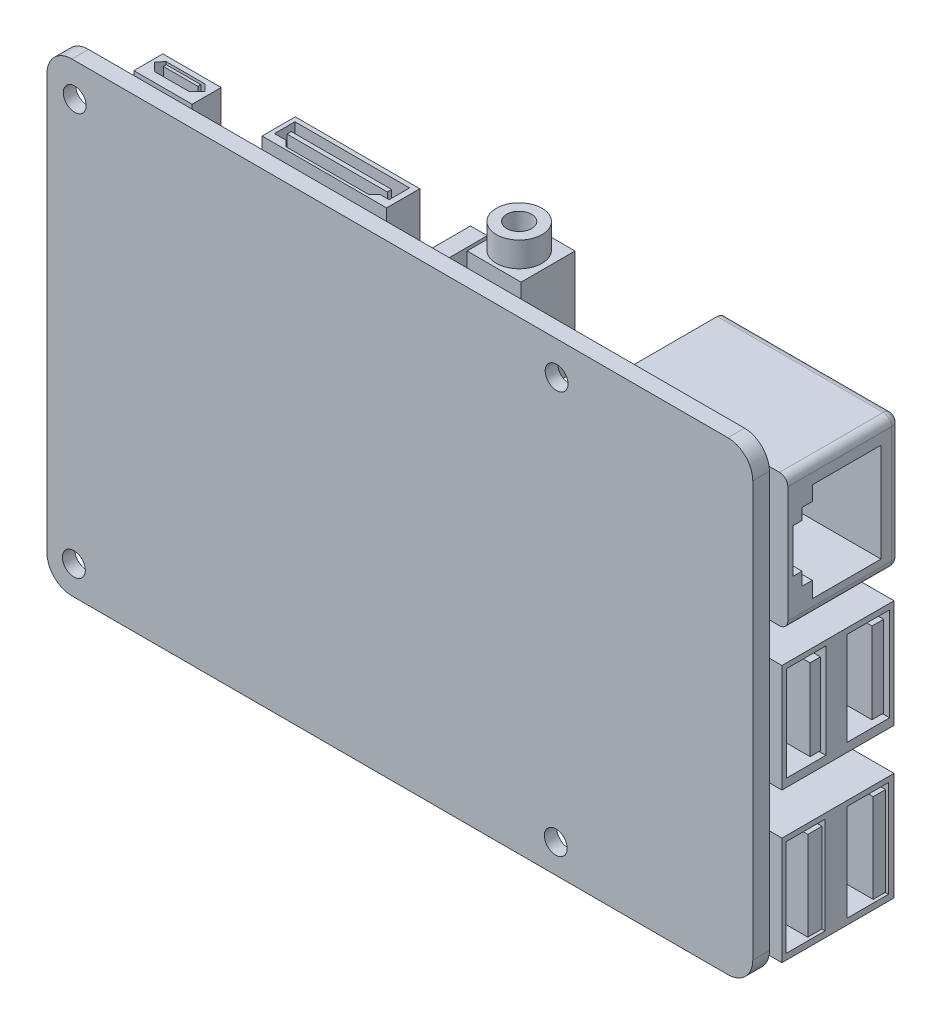
SolidWorks part; units mm, degrees
ref_plane "Front Plane" through (0, 0, 0) normal (0, 0, 1) x (1, 0, 0)
ref_plane "Top Plane" through (0, 0, 0) normal (0, 1, 0) x (1, 0, 0)
ref_plane "Right Plane" through (0, 0, 0) normal (1, 0, 0) x (0, 0, -1)
sketch "Sketch1" plane through (0, 0, 0) normal (0, 0, 1) x (1, 0, 0)
  line L1 (-42.5, 28) -> (42.5, 28)
  line L2 (-42.5, 28) -> (-42.5, -28)
  line L3 (-42.5, -28) -> (42.5, -28)
  line L4 (42.5, 28) -> (42.5, -28)
  line L5 (-42.5, 28) -> (42.5, -28) construction
  line L6 (-42.5, -28) -> (42.5, 28) construction
  point P0 (0, 0)
  dimension "D1" = 85
  dimension "D2" = 56
extrude "Boss-Extrude1" add sketch "Sketch1" along normal blind 2
fillet "Fillet1" radius 3 4 edges at (42.5, -28, 1) (42.5, 28, 1) (-42.5, 28, 1) (-42.5, -28, 1)
sketch "Sketch2" plane through (0, 0, 0) normal (0, 0, -1) x (-1, 0, 0)
  circle A0 centre (39.161, -24.5985) radius 3.1
  circle A1 centre (-18.839, -24.5986) radius 3.1
  circle A2 centre (39.161, 23.9785) radius 3.1
  circle A3 centre (-18.839, 23.9761) radius 3.1
  dimension "D1" = 6.2
  dimension "D3" = 6.2
  dimension "D2" = 58
  dimension "D4" = 58
extrude "Cut-Extrude2" cut sketch "Sketch2" against normal blind 0.5
sketch "Sketch3" plane through (0, 0, 0.5) normal (0, 0, -1) x (-1, 0, 0)
  line L0 (42.5, 25) -> (42.5, -25) construction
  line L1 (-42.5, -25) -> (-42.5, 25) construction
  line L2 (-39.5, 28) -> (39.5, 28) construction
  line L3 (39.5, -28) -> (-39.5, -28) construction
  circle A0 centre (39.161, 23.9785) radius 1.375
  circle A1 centre (-18.8764, 23.9785) radius 1.375
  circle A2 centre (-18.7753, -24.5312) radius 1.375
  circle A3 centre (39.2622, -24.5312) radius 1.375
  dimension "D1" = 2.75
  dimension "D2" = 2.75
  dimension "D9" = 2.75
  dimension "D10" = 2.75
  dimension "D3" = 58.0375
  dimension "D4" = 48.5097
  dimension "D5" = 3.339
  dimension "D6" = 23.6236
  dimension "D7" = 4.0215
  dimension "D8" = 3.4688
extrude "Cut-Extrude3" cut sketch "Sketch3" against normal blind 10.5
sketch "Sketch4" plane through (0, 0, 0) normal (0, 0, -1) x (-1, 0, 0)
  line L0 (-39.5, 28) -> (39.5, 28) construction
  line L1 (-23.7207, 9.5) -> (-44.7207, 9.5)
  line L2 (-23.7207, 9.5) -> (-23.7207, 25.5)
  line L3 (-23.7207, 25.5) -> (-44.7207, 25.5)
  line L4 (-44.7207, 9.5) -> (-44.7207, 25.5)
  line L5 (-23.7207, 9.5) -> (-44.7207, 25.5) construction
  line L6 (-23.7207, 25.5) -> (-44.7207, 9.5) construction
  point P0 (-34.2207, 17.5)
  dimension "D1" = 2.5
  dimension "D2" = 21
  dimension "D3" = 16
  dimension "D4" = 10.5
extrude "Boss-Extrude2" add sketch "Sketch4" along normal blind 13.5
fillet "Fillet2" radius 1 5 edges at (34.2207, 25.5, -13.5) (34.2207, 9.5, -13.5) (44.7207, 9.5, -6.75) (44.7207, 25.5, -6.75) (44.7207, 17.5, -13.5)
sketch "Sketch5" plane through (44.7207, 0, 0) normal (1, 0, 0) x (0, 0, -1)
  line L0 (0.6237, 20.117) -> (0.6237, 14.8349)
  line L1 (0.6237, 14.8349) -> (1.7111, 14.8349)
  line L2 (1.7111, 14.8349) -> (1.7111, 13.2605)
  line L3 (1.7111, 13.2605) -> (2.9538, 13.2605)
  line L4 (2.9538, 13.2605) -> (2.9538, 11.3427)
  line L5 (2.9538, 11.3427) -> (11.2173, 11.3427)
  line L6 (11.2173, 11.3427) -> (11.2173, 23.2197)
  line L7 (11.2173, 23.2197) -> (2.9538, 23.2197)
  line L8 (2.9538, 23.2197) -> (2.9538, 21.4786)
  line L9 (2.9538, 21.4786) -> (1.7111, 21.4786)
  line L10 (1.7111, 21.4786) -> (1.7111, 20.117)
  line L11 (1.7111, 20.117) -> (0.6237, 20.117)
extrude "Cut-Extrude4" cut sketch "Sketch5" against normal blind 18.5
sketch "Sketch7" plane through (0, 0, 0) normal (0, 0, -1) x (-1, 0, 0)
  line L0 (-39.5, 28) -> (39.5, 28) construction
  line L1 (-44.0111, 5.5) -> (-27.0111, 5.5)
  line L2 (-44.0111, 5.5) -> (-44.0111, -7.5)
  line L3 (-44.0111, -7.5) -> (-27.0111, -7.5)
  line L4 (-27.0111, 5.5) -> (-27.0111, -7.5)
  line L5 (-44.0111, 5.5) -> (-27.0111, -7.5) construction
  line L6 (-44.0111, -7.5) -> (-27.0111, 5.5) construction
  point P0 (-35.5111, -1)
  dimension "D1" = 29
  dimension "D2" = 13
  dimension "D3" = 17
extrude "Boss-Extrude3" add sketch "Sketch7" along normal blind 13.5
sketch "Sketch8" plane through (44.0111, 0, 0) normal (1, 0, 0) x (0, 0, -1)
  line L1 (7.8471, 4.8156) -> (12.9735, 4.8156)
  line L2 (7.8471, 4.8156) -> (7.8471, -6.4468)
  line L3 (7.8471, -6.4468) -> (12.9735, -6.4468)
  line L4 (12.9735, 4.8156) -> (12.9735, -6.4468)
  line L5 (7.8471, 4.8156) -> (12.9735, -6.4468) construction
  line L6 (7.8471, -6.4468) -> (12.9735, 4.8156) construction
  line L7 (0.546, 4.8933) -> (5.284, 4.8933)
  line L8 (0.546, 4.8933) -> (0.546, -6.5244)
  line L9 (0.546, -6.5244) -> (5.284, -6.5244)
  line L10 (5.284, 4.8933) -> (5.284, -6.5244)
  line L11 (0.546, 4.8933) -> (5.284, -6.5244) construction
  line L12 (0.546, -6.5244) -> (5.284, 4.8933) construction
  point P0 (10.4103, -0.8156)
  point P5 (2.915, -0.8156)
extrude "Cut-Extrude5" cut sketch "Sketch8" against normal blind 13.5
sketch "Sketch9" plane through (30.5111, 0, 0) normal (1, 0, 0) x (0, 0, -1)
  line L1 (10.8479, 4.1943) -> (12.246, 4.1943)
  line L2 (10.8479, 4.1943) -> (10.8479, -5.5924)
  line L3 (10.8479, -5.5924) -> (12.246, -5.5924)
  line L4 (12.246, 4.1943) -> (12.246, -5.5924)
  line L5 (10.8479, 4.1943) -> (12.246, -5.5924) construction
  line L6 (10.8479, -5.5924) -> (12.246, 4.1943) construction
  line L7 (3.3914, 4.0778) -> (4.6341, 4.0778)
  line L8 (3.3914, 4.0778) -> (3.3914, -5.7089)
  line L9 (3.3914, -5.7089) -> (4.6341, -5.7089)
  line L10 (4.6341, 4.0778) -> (4.6341, -5.7089)
  line L11 (3.3914, 4.0778) -> (4.6341, -5.7089) construction
  line L12 (3.3914, -5.7089) -> (4.6341, 4.0778) construction
  point P0 (11.5469, -0.699)
  point P5 (4.0128, -0.8156)
  dimension "D1" = 0.6214
extrude "Boss-Extrude4" add sketch "Sketch9" along normal blind 13.5
sketch "Sketch10" plane through (0, 0, 0) normal (0, 0, -1) x (-1, 0, 0)
  line L0 (-39.5, 28) -> (39.5, 28) construction
  line L1 (-44.0178, -12.5) -> (-27.0044, -12.5)
  line L2 (-44.0178, -12.5) -> (-44.0178, -25.5)
  line L3 (-44.0178, -25.5) -> (-27.0044, -25.5)
  line L4 (-27.0044, -12.5) -> (-27.0044, -25.5)
  line L5 (-44.0178, -12.5) -> (-27.0044, -25.5) construction
  line L6 (-44.0178, -25.5) -> (-27.0044, -12.5) construction
  point P0 (-35.5111, -19)
  dimension "D1" = 47
  dimension "D2" = 13
  dimension "D3" = 17.0134
extrude "Boss-Extrude5" add sketch "Sketch10" along normal blind 13.5
sketch "Sketch11" plane through (44.0178, 0, 0) normal (1, 0, 0) x (0, 0, -1)
  line L1 (7.8471, -13.1265) -> (12.8181, -13.1265)
  line L2 (7.8471, -13.1265) -> (7.8471, -24.7773)
  line L3 (7.8471, -24.7773) -> (12.8181, -24.7773)
  line L4 (12.8181, -13.1265) -> (12.8181, -24.7773)
  line L5 (7.8471, -13.1265) -> (12.8181, -24.7773) construction
  line L6 (7.8471, -24.7773) -> (12.8181, -13.1265) construction
  line L7 (0.4891, -13.1265) -> (5.2063, -13.1265)
  line L8 (0.4891, -13.1265) -> (0.4891, -24.7773)
  line L9 (0.4891, -24.7773) -> (5.2063, -24.7773)
  line L10 (5.2063, -13.1265) -> (5.2063, -24.7773)
  line L11 (0.4891, -13.1265) -> (5.2063, -24.7773) construction
  line L12 (0.4891, -24.7773) -> (5.2063, -13.1265) construction
  point P0 (10.3326, -18.9519)
  point P5 (2.8477, -18.9519)
extrude "Cut-Extrude6" cut sketch "Sketch11" against normal blind 13.5
sketch "Sketch12" plane through (30.5178, 0, 0) normal (1, 0, 0) x (0, 0, -1)
  line L1 (12.479, -13.6702) -> (10.9825, -13.6702)
  line L2 (12.479, -13.6702) -> (12.479, -24.3889)
  line L3 (12.479, -24.3889) -> (10.9825, -24.3889)
  line L4 (10.9825, -13.6702) -> (10.9825, -24.3889)
  line L5 (12.479, -13.6702) -> (10.9825, -24.3889) construction
  line L6 (12.479, -24.3889) -> (10.9825, -13.6702) construction
  line L7 (3.1092, -13.6702) -> (4.8168, -13.6702)
  line L8 (3.1092, -13.6702) -> (3.1092, -24.3889)
  line L9 (3.1092, -24.3889) -> (4.8168, -24.3889)
  line L10 (4.8168, -13.6702) -> (4.8168, -24.3889)
  line L11 (3.1092, -13.6702) -> (4.8168, -24.3889) construction
  line L12 (3.1092, -24.3889) -> (4.8168, -13.6702) construction
  point P0 (11.7307, -19.0296)
  point P6 (3.963, -19.0296)
extrude "Boss-Extrude6" add sketch "Sketch12" along normal blind 13.5
sketch "Sketch13" plane through (0, 0, 0) normal (0, 0, -1) x (-1, 0, 0)
  line L0 (42.5, 25) -> (42.5, -25) construction
  line L1 (-14.0854, -22.7565) -> (35.0854, -22.7565)
  line L2 (-14.0854, -22.7565) -> (-14.0854, -27.2565)
  line L3 (-14.0854, -27.2565) -> (35.0854, -27.2565)
  line L4 (35.0854, -22.7565) -> (35.0854, -27.2565)
  line L5 (-14.0854, -22.7565) -> (35.0854, -27.2565) construction
  line L6 (-14.0854, -27.2565) -> (35.0854, -22.7565) construction
  point P0 (10.5, -25.0065)
  dimension "D1" = 32
  dimension "D2" = 4.5
extrude "Boss-Extrude7" add sketch "Sketch13" along normal blind 2.5
sketch "Sketch14" plane through (0, 0, -2.5) normal (0, 0, -1) x (-1, 0, 0)
  line L0 (-11.0708, -26.0079) -> (-10.1069, -26.0079)
  line L1 (-13.5708, -26.0079) -> (-12.6069, -26.0079)
  line L2 (-13.5708, -26.0079) -> (-13.5708, -27.0079)
  line L3 (-13.5708, -27.0079) -> (-12.6069, -27.0079)
  line L4 (-12.6069, -26.0079) -> (-12.6069, -27.0079)
  line L5 (-13.5708, -26.0079) -> (-12.6069, -27.0079) construction
  line L6 (-13.5708, -27.0079) -> (-12.6069, -26.0079) construction
  line L7 (-10.1069, -26.0079) -> (-10.1069, -27.0079)
  line L8 (-11.0708, -27.0079) -> (-10.1069, -27.0079)
  line L9 (-11.0708, -26.0079) -> (-11.0708, -27.0079)
  line L10 (-8.5708, -26.0079) -> (-7.6069, -26.0079)
  line L11 (-7.6069, -26.0079) -> (-7.6069, -27.0079)
  line L12 (-8.5708, -27.0079) -> (-7.6069, -27.0079)
  line L13 (-8.5708, -26.0079) -> (-8.5708, -27.0079)
  line L14 (-6.0708, -26.0079) -> (-5.1069, -26.0079)
  line L15 (-5.1069, -26.0079) -> (-5.1069, -27.0079)
  line L16 (-6.0708, -27.0079) -> (-5.1069, -27.0079)
  line L17 (-6.0708, -26.0079) -> (-6.0708, -27.0079)
  line L18 (-3.5708, -26.0079) -> (-2.6069, -26.0079)
  line L19 (-2.6069, -26.0079) -> (-2.6069, -27.0079)
  line L20 (-3.5708, -27.0079) -> (-2.6069, -27.0079)
  line L21 (-3.5708, -26.0079) -> (-3.5708, -27.0079)
  line L22 (-1.0708, -26.0079) -> (-0.1069, -26.0079)
  line L23 (-0.1069, -26.0079) -> (-0.1069, -27.0079)
  line L24 (-1.0708, -27.0079) -> (-0.1069, -27.0079)
  line L25 (-1.0708, -26.0079) -> (-1.0708, -27.0079)
  line L26 (1.4292, -26.0079) -> (2.3931, -26.0079)
  line L27 (2.3931, -26.0079) -> (2.3931, -27.0079)
  line L28 (1.4292, -27.0079) -> (2.3931, -27.0079)
  line L29 (1.4292, -26.0079) -> (1.4292, -27.0079)
  line L30 (3.9292, -26.0079) -> (4.8931, -26.0079)
  line L31 (4.8931, -26.0079) -> (4.8931, -27.0079)
  line L32 (3.9292, -27.0079) -> (4.8931, -27.0079)
  line L33 (3.9292, -26.0079) -> (3.9292, -27.0079)
  line L34 (6.4292, -26.0079) -> (7.3931, -26.0079)
  line L35 (7.3931, -26.0079) -> (7.3931, -27.0079)
  line L36 (6.4292, -27.0079) -> (7.3931, -27.0079)
  line L37 (6.4292, -26.0079) -> (6.4292, -27.0079)
  line L38 (8.9292, -26.0079) -> (9.8931, -26.0079)
  line L39 (9.8931, -26.0079) -> (9.8931, -27.0079)
  line L40 (8.9292, -27.0079) -> (9.8931, -27.0079)
  line L41 (8.9292, -26.0079) -> (8.9292, -27.0079)
  line L42 (11.4292, -26.0079) -> (12.3931, -26.0079)
  line L43 (12.3931, -26.0079) -> (12.3931, -27.0079)
  line L44 (11.4292, -27.0079) -> (12.3931, -27.0079)
  line L45 (11.4292, -26.0079) -> (11.4292, -27.0079)
  line L46 (13.9292, -26.0079) -> (14.8931, -26.0079)
  line L47 (14.8931, -26.0079) -> (14.8931, -27.0079)
  line L48 (13.9292, -27.0079) -> (14.8931, -27.0079)
  line L49 (13.9292, -26.0079) -> (13.9292, -27.0079)
  line L50 (16.4292, -26.0079) -> (17.3931, -26.0079)
  line L51 (17.3931, -26.0079) -> (17.3931, -27.0079)
  line L52 (16.4292, -27.0079) -> (17.3931, -27.0079)
  line L53 (16.4292, -26.0079) -> (16.4292, -27.0079)
  line L54 (18.9292, -26.0079) -> (19.8931, -26.0079)
  line L55 (19.8931, -26.0079) -> (19.8931, -27.0079)
  line L56 (18.9292, -27.0079) -> (19.8931, -27.0079)
  line L57 (18.9292, -26.0079) -> (18.9292, -27.0079)
  line L58 (21.4292, -26.0079) -> (22.3931, -26.0079)
  line L59 (22.3931, -26.0079) -> (22.3931, -27.0079)
  line L60 (21.4292, -27.0079) -> (22.3931, -27.0079)
  line L61 (21.4292, -26.0079) -> (21.4292, -27.0079)
  line L62 (23.9292, -26.0079) -> (24.8931, -26.0079)
  line L63 (24.8931, -26.0079) -> (24.8931, -27.0079)
  line L64 (23.9292, -27.0079) -> (24.8931, -27.0079)
  line L65 (23.9292, -26.0079) -> (23.9292, -27.0079)
  line L66 (26.4292, -26.0079) -> (27.3931, -26.0079)
  line L67 (27.3931, -26.0079) -> (27.3931, -27.0079)
  line L68 (26.4292, -27.0079) -> (27.3931, -27.0079)
  line L69 (26.4292, -26.0079) -> (26.4292, -27.0079)
  line L70 (28.9292, -26.0079) -> (29.8931, -26.0079)
  line L71 (29.8931, -26.0079) -> (29.8931, -27.0079)
  line L72 (28.9292, -27.0079) -> (29.8931, -27.0079)
  line L73 (28.9292, -26.0079) -> (28.9292, -27.0079)
  line L74 (31.4292, -26.0079) -> (32.3931, -26.0079)
  line L75 (32.3931, -26.0079) -> (32.3931, -27.0079)
  line L76 (31.4292, -27.0079) -> (32.3931, -27.0079)
  line L77 (31.4292, -26.0079) -> (31.4292, -27.0079)
  line L78 (33.9292, -26.0079) -> (34.8931, -26.0079)
  line L79 (34.8931, -26.0079) -> (34.8931, -27.0079)
  line L80 (33.9292, -27.0079) -> (34.8931, -27.0079)
  line L81 (33.9292, -26.0079) -> (33.9292, -27.0079)
  line L82 (1.4292, -23.0147) -> (1.4292, -24.0147)
  line L83 (26.4292, -23.0147) -> (27.3931, -23.0147)
  line L84 (31.4292, -23.0147) -> (32.3931, -23.0147)
  line L85 (-7.6069, -23.0147) -> (-7.6069, -24.0147)
  line L86 (-3.5708, -24.0147) -> (-2.6069, -24.0147)
  line L87 (-1.0708, -23.0147) -> (-1.0708, -24.0147)
  line L88 (8.9292, -23.0147) -> (9.8931, -23.0147)
  line L89 (13.9292, -23.0147) -> (14.8931, -23.0147)
  line L90 (13.9292, -24.0147) -> (14.8931, -24.0147)
  line L91 (16.4292, -23.0147) -> (17.3931, -23.0147)
  line L92 (11.4292, -23.0147) -> (11.4292, -24.0147)
  line L93 (21.4292, -24.0147) -> (22.3931, -24.0147)
  line L94 (34.8931, -23.0147) -> (34.8931, -24.0147)
  line L95 (-11.0708, -24.0147) -> (-10.1069, -24.0147)
  line L96 (-0.1069, -23.0147) -> (-0.1069, -24.0147)
  line L97 (6.4292, -24.0147) -> (7.3931, -24.0147)
  line L98 (21.4292, -23.0147) -> (21.4292, -24.0147)
  line L99 (27.3931, -23.0147) -> (27.3931, -24.0147)
  line L100 (3.9292, -23.0147) -> (4.8931, -23.0147)
  line L101 (16.4292, -23.0147) -> (16.4292, -24.0147)
  line L102 (32.3931, -23.0147) -> (32.3931, -24.0147)
  line L103 (-13.5708, -23.0147) -> (-12.6069, -23.0147)
  line L104 (3.9292, -24.0147) -> (4.8931, -24.0147)
  line L105 (3.9292, -23.0147) -> (3.9292, -24.0147)
  line L106 (11.4292, -23.0147) -> (12.3931, -23.0147)
  line L107 (11.4292, -24.0147) -> (12.3931, -24.0147)
  line L108 (18.9292, -23.0147) -> (18.9292, -24.0147)
  line L109 (26.4292, -23.0147) -> (26.4292, -24.0147)
  line L110 (-13.5708, -24.0147) -> (-12.6069, -24.0147)
  line L111 (-5.1069, -23.0147) -> (-5.1069, -24.0147)
  line L112 (21.4292, -23.0147) -> (22.3931, -23.0147)
  line L113 (26.4292, -24.0147) -> (27.3931, -24.0147)
  line L114 (-2.6069, -23.0147) -> (-2.6069, -24.0147)
  line L115 (1.4292, -24.0147) -> (2.3931, -24.0147)
  line L116 (6.4292, -23.0147) -> (7.3931, -23.0147)
  line L117 (8.9292, -23.0147) -> (8.9292, -24.0147)
  line L118 (23.9292, -23.0147) -> (23.9292, -24.0147)
  line L119 (28.9292, -23.0147) -> (29.8931, -23.0147)
  line L120 (-13.5708, -23.0147) -> (-12.6069, -24.0147) construction
  line L121 (-11.0708, -23.0147) -> (-11.0708, -24.0147)
  line L122 (-8.5708, -24.0147) -> (-7.6069, -24.0147)
  line L123 (-6.0708, -23.0147) -> (-6.0708, -24.0147)
  line L124 (-1.0708, -24.0147) -> (-0.1069, -24.0147)
  line L125 (6.4292, -23.0147) -> (6.4292, -24.0147)
  line L126 (8.9292, -24.0147) -> (9.8931, -24.0147)
  line L127 (24.8931, -23.0147) -> (24.8931, -24.0147)
  line L128 (33.9292, -24.0147) -> (34.8931, -24.0147)
  line L129 (18.9292, -23.0147) -> (19.8931, -23.0147)
  line L130 (31.4292, -23.0147) -> (31.4292, -24.0147)
  line L131 (-10.1069, -23.0147) -> (-10.1069, -24.0147)
  line L132 (-3.5708, -23.0147) -> (-3.5708, -24.0147)
  line L133 (7.3931, -23.0147) -> (7.3931, -24.0147)
  line L134 (12.3931, -23.0147) -> (12.3931, -24.0147)
  line L135 (13.9292, -23.0147) -> (13.9292, -24.0147)
  line L136 (23.9292, -23.0147) -> (24.8931, -23.0147)
  line L137 (-12.6069, -23.0147) -> (-12.6069, -24.0147)
  line L138 (16.4292, -24.0147) -> (17.3931, -24.0147)
  line L139 (29.8931, -23.0147) -> (29.8931, -24.0147)
  line L140 (-11.0708, -23.0147) -> (-10.1069, -23.0147)
  line L141 (-6.0708, -23.0147) -> (-5.1069, -23.0147)
  line L142 (9.8931, -23.0147) -> (9.8931, -24.0147)
  line L143 (17.3931, -23.0147) -> (17.3931, -24.0147)
  line L144 (28.9292, -24.0147) -> (29.8931, -24.0147)
  line L145 (33.9292, -23.0147) -> (33.9292, -24.0147)
  line L146 (-8.5708, -23.0147) -> (-7.6069, -23.0147)
  line L147 (-8.5708, -23.0147) -> (-8.5708, -24.0147)
  line L148 (23.9292, -24.0147) -> (24.8931, -24.0147)
  line L149 (31.4292, -24.0147) -> (32.3931, -24.0147)
  line L150 (-3.5708, -23.0147) -> (-2.6069, -23.0147)
  line L151 (2.3931, -23.0147) -> (2.3931, -24.0147)
  line L152 (18.9292, -24.0147) -> (19.8931, -24.0147)
  line L153 (33.9292, -23.0147) -> (34.8931, -23.0147)
  line L154 (-1.0708, -23.0147) -> (-0.1069, -23.0147)
  line L155 (4.8931, -23.0147) -> (4.8931, -24.0147)
  line L156 (19.8931, -23.0147) -> (19.8931, -24.0147)
  line L157 (22.3931, -23.0147) -> (22.3931, -24.0147)
  line L158 (-13.5708, -24.0147) -> (-12.6069, -23.0147) construction
  line L159 (-13.5708, -23.0147) -> (-13.5708, -24.0147)
  line L160 (-6.0708, -24.0147) -> (-5.1069, -24.0147)
  line L161 (1.4292, -23.0147) -> (2.3931, -23.0147)
  line L162 (14.8931, -23.0147) -> (14.8931, -24.0147)
  line L163 (28.9292, -23.0147) -> (28.9292, -24.0147)
  point P0 (-13.0889, -26.5079)
  point P6 (-13.0889, -23.5147)
  dimension "D1" = 0.9639
  dimension "D2" = 1
  dimension "D4" = 0.9639
  dimension "D5" = 1
  dimension "D3" = 20
extrude "Cut-Extrude7" cut sketch "Sketch14" against normal blind 2.5
sketch "Sketch15" plane through (0, 0, -2.5) normal (0, 0, -1) x (-1, 0, 0)
  line L0 (-12.6069, -27.0079) -> (-12.6069, -26.0079) construction
  line L1 (-13.5708, -26.0079) -> (-12.6069, -26.0079)
  line L2 (-13.5708, -26.0079) -> (-13.5708, -27.0079)
  line L3 (-13.5708, -27.0079) -> (-12.6069, -27.0079)
  line L4 (-12.6069, -26.0079) -> (-12.6069, -27.0079)
  line L5 (-13.5708, -26.0079) -> (-12.6069, -27.0079) construction
  line L6 (-13.5708, -27.0079) -> (-12.6069, -26.0079) construction
  line L7 (-13.5708, -27.0079) -> (-12.6069, -27.0079) construction
  line L8 (-12.6069, -26.0079) -> (-13.5708, -26.0079) construction
  line L9 (-13.5708, -26.0079) -> (-13.5708, -27.0079) construction
  line L10 (-11.0708, -26.0079) -> (-10.1069, -26.0079)
  line L11 (-10.1069, -26.0079) -> (-10.1069, -27.0079)
  line L12 (-11.0708, -27.0079) -> (-10.1069, -27.0079)
  line L13 (-11.0708, -26.0079) -> (-11.0708, -27.0079)
  line L14 (-8.5708, -26.0079) -> (-7.6069, -26.0079)
  line L15 (-7.6069, -26.0079) -> (-7.6069, -27.0079)
  line L16 (-8.5708, -27.0079) -> (-7.6069, -27.0079)
  line L17 (-8.5708, -26.0079) -> (-8.5708, -27.0079)
  line L18 (-6.0708, -26.0079) -> (-5.1069, -26.0079)
  line L19 (-5.1069, -26.0079) -> (-5.1069, -27.0079)
  line L20 (-6.0708, -27.0079) -> (-5.1069, -27.0079)
  line L21 (-6.0708, -26.0079) -> (-6.0708, -27.0079)
  line L22 (-3.5708, -26.0079) -> (-2.6069, -26.0079)
  line L23 (-2.6069, -26.0079) -> (-2.6069, -27.0079)
  line L24 (-3.5708, -27.0079) -> (-2.6069, -27.0079)
  line L25 (-3.5708, -26.0079) -> (-3.5708, -27.0079)
  line L26 (-1.0708, -26.0079) -> (-0.1069, -26.0079)
  line L27 (-0.1069, -26.0079) -> (-0.1069, -27.0079)
  line L28 (-1.0708, -27.0079) -> (-0.1069, -27.0079)
  line L29 (-1.0708, -26.0079) -> (-1.0708, -27.0079)
  line L30 (1.4292, -26.0079) -> (2.3931, -26.0079)
  line L31 (2.3931, -26.0079) -> (2.3931, -27.0079)
  line L32 (1.4292, -27.0079) -> (2.3931, -27.0079)
  line L33 (1.4292, -26.0079) -> (1.4292, -27.0079)
  line L34 (3.9292, -26.0079) -> (4.8931, -26.0079)
  line L35 (4.8931, -26.0079) -> (4.8931, -27.0079)
  line L36 (3.9292, -27.0079) -> (4.8931, -27.0079)
  line L37 (3.9292, -26.0079) -> (3.9292, -27.0079)
  line L38 (6.4292, -26.0079) -> (7.3931, -26.0079)
  line L39 (7.3931, -26.0079) -> (7.3931, -27.0079)
  line L40 (6.4292, -27.0079) -> (7.3931, -27.0079)
  line L41 (6.4292, -26.0079) -> (6.4292, -27.0079)
  line L42 (8.9292, -26.0079) -> (9.8931, -26.0079)
  line L43 (9.8931, -26.0079) -> (9.8931, -27.0079)
  line L44 (8.9292, -27.0079) -> (9.8931, -27.0079)
  line L45 (8.9292, -26.0079) -> (8.9292, -27.0079)
  line L46 (11.4292, -26.0079) -> (12.3931, -26.0079)
  line L47 (12.3931, -26.0079) -> (12.3931, -27.0079)
  line L48 (11.4292, -27.0079) -> (12.3931, -27.0079)
  line L49 (11.4292, -26.0079) -> (11.4292, -27.0079)
  line L50 (13.9292, -26.0079) -> (14.8931, -26.0079)
  line L51 (14.8931, -26.0079) -> (14.8931, -27.0079)
  line L52 (13.9292, -27.0079) -> (14.8931, -27.0079)
  line L53 (13.9292, -26.0079) -> (13.9292, -27.0079)
  line L54 (16.4292, -26.0079) -> (17.3931, -26.0079)
  line L55 (17.3931, -26.0079) -> (17.3931, -27.0079)
  line L56 (16.4292, -27.0079) -> (17.3931, -27.0079)
  line L57 (16.4292, -26.0079) -> (16.4292, -27.0079)
  line L58 (18.9292, -26.0079) -> (19.8931, -26.0079)
  line L59 (19.8931, -26.0079) -> (19.8931, -27.0079)
  line L60 (18.9292, -27.0079) -> (19.8931, -27.0079)
  line L61 (18.9292, -26.0079) -> (18.9292, -27.0079)
  line L62 (21.4292, -26.0079) -> (22.3931, -26.0079)
  line L63 (22.3931, -26.0079) -> (22.3931, -27.0079)
  line L64 (21.4292, -27.0079) -> (22.3931, -27.0079)
  line L65 (21.4292, -26.0079) -> (21.4292, -27.0079)
  line L66 (23.9292, -26.0079) -> (24.8931, -26.0079)
  line L67 (24.8931, -26.0079) -> (24.8931, -27.0079)
  line L68 (23.9292, -27.0079) -> (24.8931, -27.0079)
  line L69 (23.9292, -26.0079) -> (23.9292, -27.0079)
  line L70 (26.4292, -26.0079) -> (27.3931, -26.0079)
  line L71 (27.3931, -26.0079) -> (27.3931, -27.0079)
  line L72 (26.4292, -27.0079) -> (27.3931, -27.0079)
  line L73 (26.4292, -26.0079) -> (26.4292, -27.0079)
  line L74 (28.9292, -26.0079) -> (29.8931, -26.0079)
  line L75 (29.8931, -26.0079) -> (29.8931, -27.0079)
  line L76 (28.9292, -27.0079) -> (29.8931, -27.0079)
  line L77 (28.9292, -26.0079) -> (28.9292, -27.0079)
  line L78 (31.4292, -26.0079) -> (32.3931, -26.0079)
  line L79 (32.3931, -26.0079) -> (32.3931, -27.0079)
  line L80 (31.4292, -27.0079) -> (32.3931, -27.0079)
  line L81 (31.4292, -26.0079) -> (31.4292, -27.0079)
  line L82 (33.9292, -26.0079) -> (34.8931, -26.0079)
  line L83 (34.8931, -26.0079) -> (34.8931, -27.0079)
  line L84 (33.9292, -27.0079) -> (34.8931, -27.0079)
  line L85 (33.9292, -26.0079) -> (33.9292, -27.0079)
  line L86 (-13.5393, -24.0089) -> (-12.5753, -24.0089)
  line L87 (1.4607, -23.0089) -> (2.4247, -23.0089)
  line L88 (3.9607, -23.0089) -> (4.9247, -23.0089)
  line L89 (19.9247, -23.0089) -> (19.9247, -24.0089)
  line L90 (28.9607, -23.0089) -> (28.9607, -24.0089)
  line L91 (-6.0393, -23.0089) -> (-6.0393, -24.0089)
  line L92 (11.4607, -23.0089) -> (12.4247, -23.0089)
  line L93 (17.4247, -23.0089) -> (17.4247, -24.0089)
  line L94 (23.9607, -23.0089) -> (24.9247, -23.0089)
  line L95 (29.9247, -23.0089) -> (29.9247, -24.0089)
  line L96 (34.9247, -23.0089) -> (34.9247, -24.0089)
  line L97 (-0.0753, -23.0089) -> (-0.0753, -24.0089)
  line L98 (28.9607, -24.0089) -> (29.9247, -24.0089)
  line L99 (31.4607, -23.0089) -> (32.4247, -23.0089)
  line L100 (-13.5393, -23.0089) -> (-13.5393, -24.0089)
  line L101 (-8.5393, -23.0089) -> (-7.5753, -23.0089)
  line L102 (7.4247, -23.0089) -> (7.4247, -24.0089)
  line L103 (11.4607, -24.0089) -> (12.4247, -24.0089)
  line L104 (22.4247, -23.0089) -> (22.4247, -24.0089)
  line L105 (-3.5393, -24.0089) -> (-2.5753, -24.0089)
  line L106 (6.4607, -24.0089) -> (7.4247, -24.0089)
  line L107 (21.4607, -23.0089) -> (22.4247, -23.0089)
  line L108 (-12.5753, -23.0089) -> (-12.5753, -24.0089)
  line L109 (-7.5753, -23.0089) -> (-7.5753, -24.0089)
  line L110 (1.4607, -24.0089) -> (2.4247, -24.0089)
  line L111 (6.4607, -23.0089) -> (7.4247, -23.0089)
  line L112 (18.9607, -24.0089) -> (19.9247, -24.0089)
  line L113 (24.9247, -23.0089) -> (24.9247, -24.0089)
  line L114 (23.9607, -23.0089) -> (23.9607, -24.0089)
  line L115 (28.9607, -23.0089) -> (29.9247, -23.0089)
  line L116 (-8.5393, -24.0089) -> (-7.5753, -24.0089)
  line L117 (1.4607, -23.0089) -> (1.4607, -24.0089)
  line L118 (9.9247, -23.0089) -> (9.9247, -24.0089)
  line L119 (33.9607, -23.0089) -> (33.9607, -24.0089)
  line L120 (-1.0393, -24.0089) -> (-0.0753, -24.0089)
  line L121 (14.9247, -23.0089) -> (14.9247, -24.0089)
  line L122 (16.4607, -23.0089) -> (16.4607, -24.0089)
  line L123 (21.4607, -23.0089) -> (21.4607, -24.0089)
  line L124 (26.4607, -23.0089) -> (27.4247, -23.0089)
  line L125 (32.4247, -23.0089) -> (32.4247, -24.0089)
  line L126 (-5.0753, -23.0089) -> (-5.0753, -24.0089)
  line L127 (8.9607, -23.0089) -> (9.9247, -23.0089)
  line L128 (8.9607, -24.0089) -> (9.9247, -24.0089)
  line L129 (16.4607, -23.0089) -> (17.4247, -23.0089)
  line L130 (21.4607, -24.0089) -> (22.4247, -24.0089)
  line L131 (26.4607, -24.0089) -> (27.4247, -24.0089)
  line L132 (31.4607, -23.0089) -> (31.4607, -24.0089)
  line L133 (-3.5393, -23.0089) -> (-3.5393, -24.0089)
  line L134 (-13.5393, -23.0089) -> (-12.5753, -24.0089) construction
  line L135 (-11.0393, -23.0089) -> (-10.0753, -23.0089)
  line L136 (-8.5393, -23.0089) -> (-8.5393, -24.0089)
  line L137 (-3.5393, -23.0089) -> (-2.5753, -23.0089)
  line L138 (2.4247, -23.0089) -> (2.4247, -24.0089)
  line L139 (13.9607, -24.0089) -> (14.9247, -24.0089)
  line L140 (23.9607, -24.0089) -> (24.9247, -24.0089)
  line L141 (26.4607, -23.0089) -> (26.4607, -24.0089)
  line L142 (31.4607, -24.0089) -> (32.4247, -24.0089)
  line L143 (-13.5393, -23.0089) -> (-12.5753, -23.0089)
  line L144 (-2.5753, -23.0089) -> (-2.5753, -24.0089)
  line L145 (-1.0393, -23.0089) -> (-1.0393, -24.0089)
  line L146 (6.4607, -23.0089) -> (6.4607, -24.0089)
  line L147 (12.4247, -23.0089) -> (12.4247, -24.0089)
  line L148 (27.4247, -23.0089) -> (27.4247, -24.0089)
  line L149 (-11.0393, -24.0089) -> (-10.0753, -24.0089)
  line L150 (-6.0393, -24.0089) -> (-5.0753, -24.0089)
  line L151 (8.9607, -23.0089) -> (8.9607, -24.0089)
  line L152 (33.9607, -24.0089) -> (34.9247, -24.0089)
  line L153 (-13.5393, -24.0089) -> (-12.5753, -23.0089) construction
  line L154 (-1.0393, -23.0089) -> (-0.0753, -23.0089)
  line L155 (3.9607, -23.0089) -> (3.9607, -24.0089)
  line L156 (13.9607, -23.0089) -> (14.9247, -23.0089)
  line L157 (16.4607, -24.0089) -> (17.4247, -24.0089)
  line L158 (-10.0753, -23.0089) -> (-10.0753, -24.0089)
  line L159 (-6.0393, -23.0089) -> (-5.0753, -23.0089)
  line L160 (4.9247, -23.0089) -> (4.9247, -24.0089)
  line L161 (13.9607, -23.0089) -> (13.9607, -24.0089)
  line L162 (18.9607, -23.0089) -> (18.9607, -24.0089)
  line L163 (33.9607, -23.0089) -> (34.9247, -23.0089)
  line L164 (-11.0393, -23.0089) -> (-11.0393, -24.0089)
  line L165 (3.9607, -24.0089) -> (4.9247, -24.0089)
  line L166 (11.4607, -23.0089) -> (11.4607, -24.0089)
  line L167 (18.9607, -23.0089) -> (19.9247, -23.0089)
  point P0 (-13.0889, -26.5079)
  point P13 (-13.0573, -23.5089)
  dimension "D1" = 20
extrude "Boss-Extrude8" add sketch "Sketch15" along normal blind 5 and the other way blind 2.5
sketch "Sketch16" plane through (0, 0, 0) normal (0, 0, -1) x (-1, 0, 0)
  line L1 (9.1227, 6.5) -> (22.1227, 6.5)
  line L2 (9.1227, 6.5) -> (9.1227, -6.5)
  line L3 (9.1227, -6.5) -> (22.1227, -6.5)
  line L4 (22.1227, 6.5) -> (22.1227, -6.5)
  line L5 (9.1227, 6.5) -> (22.1227, -6.5) construction
  line L6 (9.1227, -6.5) -> (22.1227, 6.5) construction
  point P0 (15.6227, 0)
  dimension "D1" = 13
  dimension "D2" = 13
extrude "Boss-Extrude9" add sketch "Sketch16" along normal blind 1
sketch "Sketch17" plane through (0, 0, 0) normal (0, 0, -1) x (-1, 0, 0)
  line L1 (-19.4325, -1.3087) -> (-10.8323, -1.3087)
  line L2 (-19.4325, -1.3087) -> (-19.4325, -9.9089)
  line L3 (-19.4325, -9.9089) -> (-10.8323, -9.9089)
  line L4 (-10.8323, -1.3087) -> (-10.8323, -9.9089)
  line L5 (-19.4325, -1.3087) -> (-10.8323, -9.9089) construction
  line L6 (-19.4325, -9.9089) -> (-10.8323, -1.3087) construction
  point P0 (-15.1324, -5.6088)
extrude "Boss-Extrude10" add sketch "Sketch17" along normal blind 1
sketch "Sketch18" plane through (0, 0, 0) normal (0, 0, -1) x (-1, 0, 0)
  line L0 (38.9928, 10.2325) -> (41.0493, 10.2325)
  line L1 (41.0493, 10.2325) -> (41.0493, 8.7325)
  line L2 (41.0493, 8.7325) -> (42.2178, 7.564)
  line L3 (42.2178, 7.564) -> (42.2178, -4.436)
  line L4 (42.2178, -4.436) -> (41.0493, -5.6045)
  line L5 (41.0493, -5.6045) -> (41.0493, -7.1045)
  line L6 (41.0493, -7.1045) -> (38.9928, -7.1045)
  line L7 (38.9928, -7.1045) -> (38.9928, 10.2325)
  dimension "D1" = 12
  dimension "D2" = 1.5
  dimension "D3" = 1.5
extrude "Boss-Extrude11" add sketch "Sketch18" along normal blind 5
sketch "Sketch19" plane through (0, 0, -5) normal (0, 0, -1) x (-1, 0, 0)
  line L1 (39.2875, 8.3506) -> (40.3311, 8.3506)
  line L2 (39.2875, 8.3506) -> (39.2875, -5.0077)
  line L3 (39.2875, -5.0077) -> (40.3311, -5.0077)
  line L4 (40.3311, 8.3506) -> (40.3311, -5.0077)
  line L5 (39.2875, 8.3506) -> (40.3311, -5.0077) construction
  line L6 (39.2875, -5.0077) -> (40.3311, 8.3506) construction
  point P0 (39.8093, 1.6715)
extrude "Cut-Extrude8" cut sketch "Sketch19" against normal blind 5
sketch "Sketch20" plane through (0, 0, 0) normal (0, 0, -1) x (-1, 0, 0)
  line L1 (-12.5931, 29.7719) -> (-6.0931, 29.7719)
  line L2 (-12.5931, 29.7719) -> (-12.5931, 17.1703)
  line L3 (-12.5931, 17.1703) -> (-6.0931, 17.1703)
  line L4 (-6.0931, 29.7719) -> (-6.0931, 17.1703)
  line L5 (-12.5931, 29.7719) -> (-6.0931, 17.1703) construction
  line L6 (-12.5931, 17.1703) -> (-6.0931, 29.7719) construction
  point P0 (-9.3431, 23.4711)
  dimension "D1" = 6.5
extrude "Boss-Extrude12" add sketch "Sketch20" along normal blind 6.5
sketch "Sketch21" plane through (0, 29.7719, 0) normal (0, 1, 0) x (1, 0, 0)
  circle A0 centre (9.148, 3.2205) radius 2.75
  dimension "D1" = 5.5
extrude "Boss-Extrude13" add sketch "Sketch21" along normal blind 3
sketch "Sketch22" plane through (0, 32.7719, 0) normal (0, 1, 0) x (1, 0, 0)
  circle A0 centre (9.148, 3.2205) radius 1.5
  dimension "D1" = 3
extrude "Cut-Extrude9" cut sketch "Sketch22" against normal blind 15
sketch "Sketch23" plane through (0, 0, 0) normal (0, 0, -1) x (-1, 0, 0)
  line L0 (0, 10.0715) -> (-2.0282, 10.0715)
  line L1 (-2.0282, 10.0715) -> (-2.0282, 13.0527)
  line L2 (-2.0282, 13.0527) -> (-3.4986, 14.5231)
  line L3 (-3.4986, 14.5231) -> (-3.4986, 21.6187)
  line L4 (-3.4986, 21.6187) -> (-2.0282, 23.0891)
  line L5 (-2.0282, 23.0891) -> (-2.0282, 26.0817)
  line L6 (-2.0282, 26.0817) -> (0, 26.0817)
  line L7 (0, 26.0817) -> (0, 10.0715)
extrude "Boss-Extrude14" add sketch "Sketch23" along normal blind 6.5
sketch "Sketch24" plane through (0, 0, -6.5) normal (0, 0, -1) x (-1, 0, 0)
  line L1 (-0.4085, 13.3017) -> (-1.3834, 13.3017)
  line L2 (-0.4085, 13.3017) -> (-0.4085, 22.8986)
  line L3 (-0.4085, 22.8986) -> (-1.3834, 22.8986)
  line L4 (-1.3834, 13.3017) -> (-1.3834, 22.8986)
  line L5 (-0.4085, 13.3017) -> (-1.3834, 22.8986) construction
  line L6 (-0.4085, 22.8986) -> (-1.3834, 13.3017) construction
  point P0 (-0.896, 18.1001)
extrude "Cut-Extrude10" cut sketch "Sketch24" against normal blind 6.5
sketch "Sketch25" plane through (0, 0, 0) normal (0, 0, -1) x (-1, 0, 0)
  line L1 (18.6005, 17.4163) -> (3.6005, 17.4163)
  line L2 (18.6005, 17.4163) -> (18.6005, 29.4163)
  line L3 (18.6005, 29.4163) -> (3.6005, 29.4163)
  line L4 (3.6005, 17.4163) -> (3.6005, 29.4163)
  line L5 (18.6005, 17.4163) -> (3.6005, 29.4163) construction
  line L6 (18.6005, 29.4163) -> (3.6005, 17.4163) construction
  point P0 (11.1005, 23.4163)
  dimension "D1" = 15
  dimension "D2" = 12
extrude "Boss-Extrude15" add sketch "Sketch25" along normal blind 4
sketch "Sketch26" plane through (0, 29.4163, 0) normal (0, 1, 0) x (1, 0, 0)
  line L0 (-18.1055, 3.4713) -> (-4.2971, 3.4713)
  line L1 (-4.2971, 3.4713) -> (-4.2971, 1.0042)
  line L2 (-4.2971, 1.0042) -> (-5.3631, 1.0042)
  line L3 (-5.3631, 1.0042) -> (-6.045, 0.3222)
  line L4 (-6.045, 0.3222) -> (-16.0377, 0.3222)
  line L5 (-16.0377, 0.3222) -> (-16.7196, 1.0042)
  line L6 (-16.7196, 1.0042) -> (-18.1055, 1.0042)
  line L7 (-18.1055, 1.0042) -> (-18.1055, 3.4713)
extrude "Cut-Extrude11" cut sketch "Sketch26" against normal blind 11
sketch "Sketch27" plane through (0, 18.4163, 0) normal (0, 1, 0) x (1, 0, 0)
  line L1 (-17.2982, 2.2235) -> (-5.2204, 2.2235)
  line L2 (-17.2982, 2.2235) -> (-17.2982, 1.708)
  line L3 (-17.2982, 1.708) -> (-5.2204, 1.708)
  line L4 (-5.2204, 2.2235) -> (-5.2204, 1.708)
  line L5 (-17.2982, 2.2235) -> (-5.2204, 1.708) construction
  line L6 (-17.2982, 1.708) -> (-5.2204, 2.2235) construction
  point P0 (-11.2593, 1.9657)
extrude "Boss-Extrude16" add sketch "Sketch27" along normal blind 11
sketch "Sketch28" plane through (0, 0, 0) normal (0, 0, -1) x (-1, 0, 0)
  line L1 (34.0404, 22.6437) -> (27.0224, 22.6437)
  line L2 (34.0404, 22.6437) -> (34.0404, 28.5159)
  line L3 (34.0404, 28.5159) -> (27.0224, 28.5159)
  line L4 (27.0224, 22.6437) -> (27.0224, 28.5159)
  line L5 (34.0404, 22.6437) -> (27.0224, 28.5159) construction
  line L6 (34.0404, 28.5159) -> (27.0224, 22.6437) construction
  point P0 (30.5314, 25.5798)
extrude "Boss-Extrude17" add sketch "Sketch28" along normal blind 3.5
sketch "Sketch29" plane through (0, 28.5159, 0) normal (0, 1, 0) x (1, 0, 0)
  line L0 (-33.0397, 2.8909) -> (-28.3637, 2.8909)
  line L1 (-28.3637, 2.8909) -> (-27.5996, 2.1269)
  line L2 (-27.5996, 2.1269) -> (-28.5776, 1.1489)
  line L3 (-28.5776, 1.1489) -> (-32.7035, 1.1489)
  line L4 (-32.7035, 1.1489) -> (-33.6815, 2.1269)
  line L5 (-33.6815, 2.1269) -> (-33.0397, 2.8909)
extrude "Cut-Extrude12" cut sketch "Sketch29" against normal blind 5.5
sketch "Sketch30" plane through (0, 23.0159, 0) normal (0, 1, 0) x (1, 0, 0)
  line L1 (-32.7065, 2.5688) -> (-28.5473, 2.5688)
  line L2 (-32.7065, 2.5688) -> (-32.7065, 2.2193)
  line L3 (-32.7065, 2.2193) -> (-28.5473, 2.2193)
  line L4 (-28.5473, 2.5688) -> (-28.5473, 2.2193)
  line L5 (-32.7065, 2.5688) -> (-28.5473, 2.2193) construction
  line L6 (-32.7065, 2.2193) -> (-28.5473, 2.5688) construction
  point P0 (-30.6269, 2.394)
extrude "Boss-Extrude18" add sketch "Sketch30" along normal blind 5.5
sketch "Sketch31" plane through (0, 0, -1) normal (0, 0, -1) x (-1, 0, 0)
  line L0 (-10.8323, -1.3087) -> (-19.4325, -1.3087) construction
  line L1 (-19.1594, -0.8087) -> (-18.6594, -0.8087)
  line L2 (-19.1594, -0.8087) -> (-19.1594, -1.3087)
  line L3 (-19.1594, -1.3087) -> (-18.6594, -1.3087)
  line L4 (-18.6594, -0.8087) -> (-18.6594, -1.3087)
  line L5 (-19.1594, -0.8087) -> (-18.6594, -1.3087) construction
  line L6 (-19.1594, -1.3087) -> (-18.6594, -0.8087) construction
  line L7 (-18.1594, -0.8087) -> (-17.6594, -0.8087)
  line L8 (-17.6594, -0.8087) -> (-17.6594, -1.3087)
  line L9 (-18.1594, -1.3087) -> (-17.6594, -1.3087)
  line L10 (-18.1594, -0.8087) -> (-18.1594, -1.3087)
  line L11 (-17.1594, -0.8087) -> (-16.6594, -0.8087)
  line L12 (-16.6594, -0.8087) -> (-16.6594, -1.3087)
  line L13 (-17.1594, -1.3087) -> (-16.6594, -1.3087)
  line L14 (-17.1594, -0.8087) -> (-17.1594, -1.3087)
  line L15 (-16.1594, -0.8087) -> (-15.6594, -0.8087)
  line L16 (-15.6594, -0.8087) -> (-15.6594, -1.3087)
  line L17 (-16.1594, -1.3087) -> (-15.6594, -1.3087)
  line L18 (-16.1594, -0.8087) -> (-16.1594, -1.3087)
  line L19 (-15.1594, -0.8087) -> (-14.6594, -0.8087)
  line L20 (-14.6594, -0.8087) -> (-14.6594, -1.3087)
  line L21 (-15.1594, -1.3087) -> (-14.6594, -1.3087)
  line L22 (-15.1594, -0.8087) -> (-15.1594, -1.3087)
  line L23 (-14.1594, -0.8087) -> (-13.6594, -0.8087)
  line L24 (-13.6594, -0.8087) -> (-13.6594, -1.3087)
  line L25 (-14.1594, -1.3087) -> (-13.6594, -1.3087)
  line L26 (-14.1594, -0.8087) -> (-14.1594, -1.3087)
  line L27 (-13.1594, -0.8087) -> (-12.6594, -0.8087)
  line L28 (-12.6594, -0.8087) -> (-12.6594, -1.3087)
  line L29 (-13.1594, -1.3087) -> (-12.6594, -1.3087)
  line L30 (-13.1594, -0.8087) -> (-13.1594, -1.3087)
  line L31 (-12.1594, -0.8087) -> (-11.6594, -0.8087)
  line L32 (-11.6594, -0.8087) -> (-11.6594, -1.3087)
  line L33 (-12.1594, -1.3087) -> (-11.6594, -1.3087)
  line L34 (-12.1594, -0.8087) -> (-12.1594, -1.3087)
  line L35 (-18.9225, -9.9089) -> (-18.4225, -9.9089)
  line L36 (-15.4225, -9.9089) -> (-15.4225, -10.4089)
  line L37 (-18.4225, -9.9089) -> (-18.4225, -10.4089)
  line L38 (-12.9225, -10.4089) -> (-12.4225, -10.4089)
  line L39 (-11.4225, -9.9089) -> (-11.4225, -10.4089)
  line L40 (-14.9225, -9.9089) -> (-14.9225, -10.4089)
  line L41 (-14.9225, -9.9089) -> (-14.4225, -9.9089)
  line L42 (-12.4225, -9.9089) -> (-12.4225, -10.4089)
  line L43 (-16.4225, -9.9089) -> (-16.4225, -10.4089)
  line L44 (-14.9225, -10.4089) -> (-14.4225, -10.4089)
  line L45 (-18.9225, -10.4089) -> (-18.4225, -9.9089) construction
  line L46 (-14.4225, -9.9089) -> (-14.4225, -10.4089)
  line L47 (-11.9225, -10.4089) -> (-11.4225, -10.4089)
  line L48 (-18.9225, -9.9089) -> (-18.9225, -10.4089)
  line L49 (-17.4225, -9.9089) -> (-17.4225, -10.4089)
  line L50 (-13.9225, -9.9089) -> (-13.4225, -9.9089)
  line L51 (-13.9225, -10.4089) -> (-13.4225, -10.4089)
  line L52 (-12.9225, -9.9089) -> (-12.4225, -9.9089)
  line L53 (-16.9225, -10.4089) -> (-16.4225, -10.4089)
  line L54 (-13.9225, -9.9089) -> (-13.9225, -10.4089)
  line L55 (-17.9225, -9.9089) -> (-17.4225, -9.9089)
  line L56 (-13.4225, -9.9089) -> (-13.4225, -10.4089)
  line L57 (-17.9225, -9.9089) -> (-17.9225, -10.4089)
  line L58 (-11.9225, -9.9089) -> (-11.9225, -10.4089)
  line L59 (-17.9225, -10.4089) -> (-17.4225, -10.4089)
  line L60 (-16.9225, -9.9089) -> (-16.9225, -10.4089)
  line L61 (-18.9225, -10.4089) -> (-18.4225, -10.4089)
  line L62 (-15.9225, -10.4089) -> (-15.4225, -10.4089)
  line L63 (-11.9225, -9.9089) -> (-11.4225, -9.9089)
  line L64 (-15.9225, -9.9089) -> (-15.4225, -9.9089)
  line L65 (-15.9225, -9.9089) -> (-15.9225, -10.4089)
  line L66 (-12.9225, -9.9089) -> (-12.9225, -10.4089)
  line L67 (-16.9225, -9.9089) -> (-16.4225, -9.9089)
  line L68 (-18.9225, -9.9089) -> (-18.4225, -10.4089) construction
  line L69 (-19.4325, -9.9089) -> (-10.8323, -9.9089) construction
  line L70 (-19.4325, -1.3087) -> (-19.4325, -9.9089) construction
  line L71 (-19.9325, -1.4389) -> (-19.4325, -1.4389)
  line L72 (-19.9325, -1.4389) -> (-19.9325, -1.9389)
  line L73 (-19.9325, -1.9389) -> (-19.4325, -1.9389)
  line L74 (-19.4325, -1.4389) -> (-19.4325, -1.9389)
  line L75 (-19.9325, -1.4389) -> (-19.4325, -1.9389) construction
  line L76 (-19.9325, -1.9389) -> (-19.4325, -1.4389) construction
  line L77 (-19.9325, -2.5389) -> (-19.4325, -2.5389)
  line L78 (-19.9325, -3.0389) -> (-19.4325, -3.0389)
  line L79 (-19.9325, -2.5389) -> (-19.9325, -3.0389)
  line L80 (-19.4325, -2.5389) -> (-19.4325, -3.0389)
  line L81 (-19.9325, -3.6389) -> (-19.4325, -3.6389)
  line L82 (-19.9325, -4.1389) -> (-19.4325, -4.1389)
  line L83 (-19.9325, -3.6389) -> (-19.9325, -4.1389)
  line L84 (-19.4325, -3.6389) -> (-19.4325, -4.1389)
  line L85 (-19.9325, -4.7389) -> (-19.4325, -4.7389)
  line L86 (-19.9325, -5.2389) -> (-19.4325, -5.2389)
  line L87 (-19.9325, -4.7389) -> (-19.9325, -5.2389)
  line L88 (-19.4325, -4.7389) -> (-19.4325, -5.2389)
  line L89 (-19.9325, -5.8389) -> (-19.4325, -5.8389)
  line L90 (-19.9325, -6.3389) -> (-19.4325, -6.3389)
  line L91 (-19.9325, -5.8389) -> (-19.9325, -6.3389)
  line L92 (-19.4325, -5.8389) -> (-19.4325, -6.3389)
  line L93 (-19.9325, -6.9389) -> (-19.4325, -6.9389)
  line L94 (-19.9325, -7.4389) -> (-19.4325, -7.4389)
  line L95 (-19.9325, -6.9389) -> (-19.9325, -7.4389)
  line L96 (-19.4325, -6.9389) -> (-19.4325, -7.4389)
  line L97 (-19.9325, -8.0389) -> (-19.4325, -8.0389)
  line L98 (-19.9325, -8.5389) -> (-19.4325, -8.5389)
  line L99 (-19.9325, -8.0389) -> (-19.9325, -8.5389)
  line L100 (-19.4325, -8.0389) -> (-19.4325, -8.5389)
  line L101 (-19.9325, -9.1389) -> (-19.4325, -9.1389)
  line L102 (-19.9325, -9.6389) -> (-19.4325, -9.6389)
  line L103 (-19.9325, -9.1389) -> (-19.9325, -9.6389)
  line L104 (-19.4325, -9.1389) -> (-19.4325, -9.6389)
  line L105 (-10.8323, -9.9089) -> (-10.8323, -1.3087) construction
  line L106 (-10.8323, -1.3562) -> (-10.3323, -1.3562)
  line L107 (-10.8323, -1.3562) -> (-10.8323, -1.8562)
  line L108 (-10.8323, -1.8562) -> (-10.3323, -1.8562)
  line L109 (-10.3323, -1.3562) -> (-10.3323, -1.8562)
  line L110 (-10.8323, -1.3562) -> (-10.3323, -1.8562) construction
  line L111 (-10.8323, -1.8562) -> (-10.3323, -1.3562) construction
  line L112 (-10.8323, -2.4562) -> (-10.3323, -2.4562)
  line L113 (-10.3323, -2.4562) -> (-10.3323, -2.9562)
  line L114 (-10.8323, -2.9562) -> (-10.3323, -2.9562)
  line L115 (-10.8323, -2.4562) -> (-10.8323, -2.9562)
  line L116 (-10.8323, -3.5562) -> (-10.3323, -3.5562)
  line L117 (-10.3323, -3.5562) -> (-10.3323, -4.0562)
  line L118 (-10.8323, -4.0562) -> (-10.3323, -4.0562)
  line L119 (-10.8323, -3.5562) -> (-10.8323, -4.0562)
  line L120 (-10.8323, -4.6562) -> (-10.3323, -4.6562)
  line L121 (-10.3323, -4.6562) -> (-10.3323, -5.1562)
  line L122 (-10.8323, -5.1562) -> (-10.3323, -5.1562)
  line L123 (-10.8323, -4.6562) -> (-10.8323, -5.1562)
  line L124 (-10.8323, -5.7562) -> (-10.3323, -5.7562)
  line L125 (-10.3323, -5.7562) -> (-10.3323, -6.2562)
  line L126 (-10.8323, -6.2562) -> (-10.3323, -6.2562)
  line L127 (-10.8323, -5.7562) -> (-10.8323, -6.2562)
  line L128 (-10.8323, -6.8562) -> (-10.3323, -6.8562)
  line L129 (-10.3323, -6.8562) -> (-10.3323, -7.3562)
  line L130 (-10.8323, -7.3562) -> (-10.3323, -7.3562)
  line L131 (-10.8323, -6.8562) -> (-10.8323, -7.3562)
  line L132 (-10.8323, -7.9562) -> (-10.3323, -7.9562)
  line L133 (-10.3323, -7.9562) -> (-10.3323, -8.4562)
  line L134 (-10.8323, -8.4562) -> (-10.3323, -8.4562)
  line L135 (-10.8323, -7.9562) -> (-10.8323, -8.4562)
  line L136 (-10.8323, -9.0562) -> (-10.3323, -9.0562)
  line L137 (-10.3323, -9.0562) -> (-10.3323, -9.5562)
  line L138 (-10.8323, -9.5562) -> (-10.3323, -9.5562)
  line L139 (-10.8323, -9.0562) -> (-10.8323, -9.5562)
  point P0 (-18.9094, -1.0587)
  point P8 (-18.6725, -10.1184)
  point P70 (-19.6825, -1.6889)
  point P77 (-10.5823, -1.6062)
  dimension "D1" = 0.5
  dimension "D2" = 0.5
  dimension "D4" = 0.5
  dimension "D5" = 0.5
  dimension "D6" = 0.5
  dimension "D7" = 0.5
  dimension "D9" = 0.5
  dimension "D10" = 0.5
  dimension "D3" = 8
  dimension "D8" = 8
  dimension "D11" = 8
extrude "Boss-Extrude19" add sketch "Sketch31" against normal up to surface (1 mm away) up to face at (15.1324, -5.6088, 0)
sketch "Sketch32" plane through (0, 0, 0) normal (0, 0, -1) x (-1, 0, 0)
  text T0 "Raspberry Pi Model B+ V1.2"
extrude "Cut-Extrude13" cut sketch "Sketch32" against normal blind 1.1
